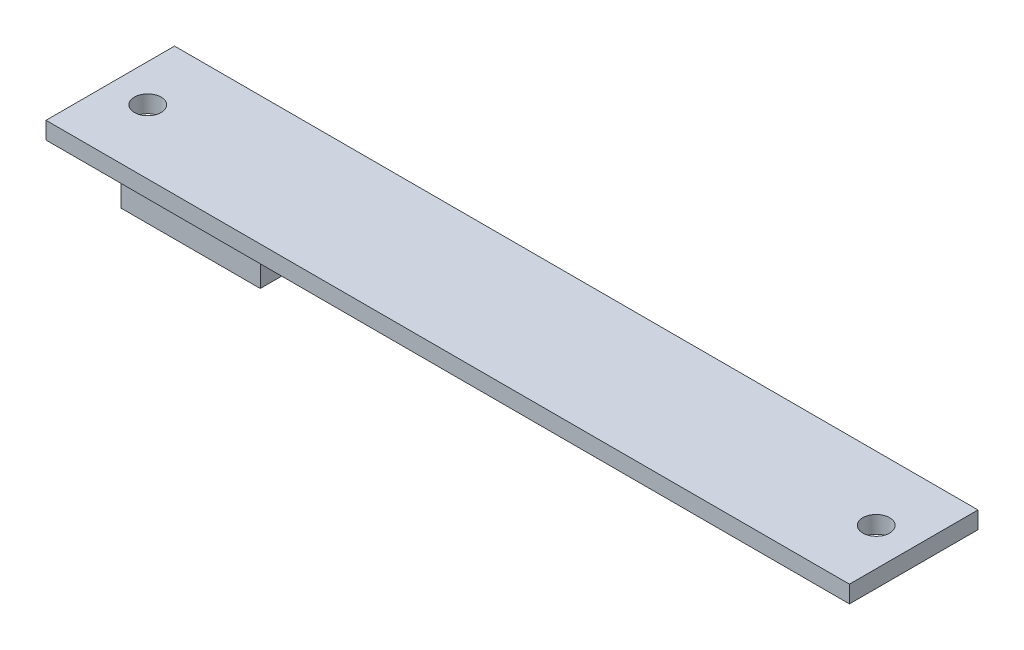
SolidWorks part; units mm, degrees
ref_plane "Front Plane" through (0, 0, 0) normal (0, 0, 1) x (1, 0, 0)
ref_plane "Top Plane" through (0, 0, 0) normal (0, 1, 0) x (1, 0, 0)
ref_plane "Right Plane" through (0, 0, 0) normal (1, 0, 0) x (0, 0, -1)
sketch "Sketch1" plane through (0, 0, 0) normal (0, 1, 0) x (1, 0, 0)
  line L1 (0, 0) -> (-75, 0)
  line L2 (0, 0) -> (0, 12)
  line L3 (0, 12) -> (-75, 12)
  line L4 (-75, 0) -> (-75, 12)
  dimension "D1" = 12
  dimension "D2" = 75
extrude "pcb" add sketch "Sketch1" along normal blind 1.6
sketch "Sketch2" plane through (0, 1.6, 0) normal (0, 1, 0) x (1, 0, 0)
  line L0 (-75, 12) -> (-75, 0) construction
  line L1 (0, 0) -> (0, 12) construction
  circle A0 centre (-71.5, 6) radius 1.25
  circle A1 centre (-3.5, 6) radius 1.25
  point P8 (0, 0)
  point P9 (0, 6)
  point P10 (0, 0)
  point P11 (-3.5, 6)
  dimension "D3" = 2.5
  dimension "D4" = 2.5
  dimension "D1" = 3.5
  dimension "D2" = 3.5
extrude "screw holes" cut sketch "Sketch2" against normal through all
sketch "Sketch3" plane through (0, 0, 0) normal (0, -1, 0) x (1, 0, 0)
  line L1 (-69, -1) -> (-56, -1)
  line L2 (-69, -1) -> (-69, -3.3)
  line L3 (-69, -3.3) -> (-56, -3.3)
  line L4 (-56, -1) -> (-56, -3.3)
  line L5 (-75, 0) -> (0, 0) construction
  line L6 (-75, -12) -> (-75, 0) construction
  dimension "D1" = 13
  dimension "D2" = 2.3
  dimension "D3" = 1
  dimension "D4" = 6
extrude "Boss-Extrude1" add sketch "Sketch3" along normal blind 3
